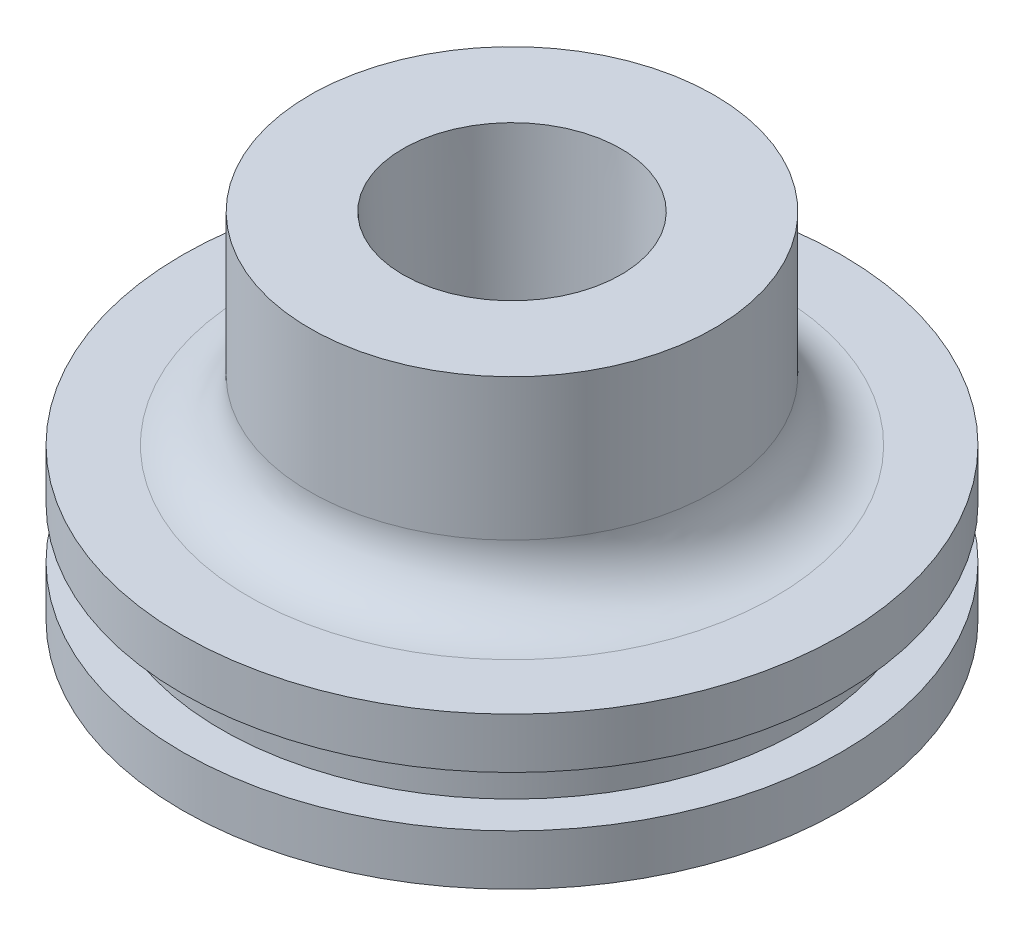
SolidWorks part; units mm, degrees
ref_plane "Front Plane" through (0, 0, 0) normal (0, 0, 1) x (1, 0, 0)
ref_plane "Top Plane" through (0, 0, 0) normal (0, 1, 0) x (1, 0, 0)
ref_plane "Right Plane" through (0, 0, 0) normal (1, 0, 0) x (0, 0, -1)
sketch "Sketch2" plane through (0, 0, 0) normal (0, 0, 1) x (1, 0, 0)
  line L1 (0, 0) -> (-20.701, 0) construction
  line L2 (-20.701, 0) -> (-20.701, -3.175)
  line L3 (-20.701, -3.175) -> (-18.2562, -3.175)
  line L4 (-18.2562, -3.175) -> (-18.2562, -6.35)
  line L5 (-18.2562, -6.35) -> (-20.701, -6.35)
  line L6 (-20.701, -6.35) -> (-20.701, -9.525)
  line L7 (-20.701, -3.175) -> (-20.701, -6.35) construction
  line L13 (0, -9.525) -> (-20.701, -9.525)
  line L14 (-20.701, 0) -> (-16.51, 0)
  line L15 (-12.7, 3.81) -> (-12.7, 12.7)
  line L20 (0, -9.525) -> (0, 12.7)
  line L21 (0, 12.7) -> (-12.7, 12.7)
  arc A0 (-12.7, 3.81) -> (-16.51, 0) centre (-16.51, 3.81) cw
  point P3 (-8.9738, 13.1371)
  point P17 (-12.7, 0)
  dimension "D11" = 3.81
  dimension "D1" = 20.701
  dimension "D2" = 12.7
  dimension "D3" = 3.175
  dimension "D4" = 12.7
  dimension "D5" = 3.175
  dimension "D6" = 9.525
  dimension "D7" = 3.175
  dimension "D8" = 18.2562
revolve "base" add sketch "Sketch2" angle 360 about L20
sketch "Sketch10" plane through (0, 12.7, 0) normal (0, 1, 0) x (1, 0, 0)
  point P0 (0, 0)
hole_wizard "PT 1/4 NPT Tapped" positions "Sketch10" profile "Sketch11" size "1/4" standard "ANSI Inch"
sketch "Sketch11" plane through (0, 12.7, 0) normal (1, 0, 0) x (0, 0, 1)
  line L0 (0, 0) -> (0, 16.0423)
  line L1 (5.5626, 12.7) -> (0, 16.0423)
  line L2 (-5.5626, 12.7) -> (0, 16.0423) construction
  line L3 (5.5626, 12.7) -> (5.5626, 9.906)
  line L4 (5.5626, 9.906) -> (6.5452, 9.906)
  line L5 (6.5452, 9.906) -> (6.8544, 0)
  line L6 (-6.5452, 9.906) -> (-6.8544, 0) construction
  line L7 (6.8544, 0) -> (0, 0)
  line L8 (0, -6.35) -> (0, 107.95) construction
  line L11 (-5.5626, 9.906) -> (-6.5452, 9.906) construction
  dimension "Tap Drill Dia." = 11.1252
  dimension "Tap Drill Depth" = 12.7
  dimension "Thread Dia." = 13.7089
  dimension "Thread Angle" = 3.576
  dimension "Thread Depth" = 9.906
  dimension "Drill Angle" = 118
sketch "Sketch12" plane through (0, 12.7, 0) normal (0, 1, 0) x (1, 0, 0)
  point P0 (0, 0)
hole_wizard "PT 1/8 Pressure hole" positions "Sketch12" profile "Sketch13" hole size "1/8" standard "ANSI Inch" end condition through all
sketch "Sketch13" plane through (0, 12.7, 0) normal (1, 0, 0) x (0, 0, 1)
  line L0 (0, 0) -> (0, 22.225)
  line L1 (0, 22.225) -> (1.5875, 22.225)
  line L2 (1.5875, 22.225) -> (1.5875, 0)
  line L5 (1.5875, 0) -> (0, 0)
  line L11 (0, -6.35) -> (0, 107.95) construction
  dimension "Thru Hole Dia." = 3.175
  dimension "Thru Hole Depth" = 22.225
